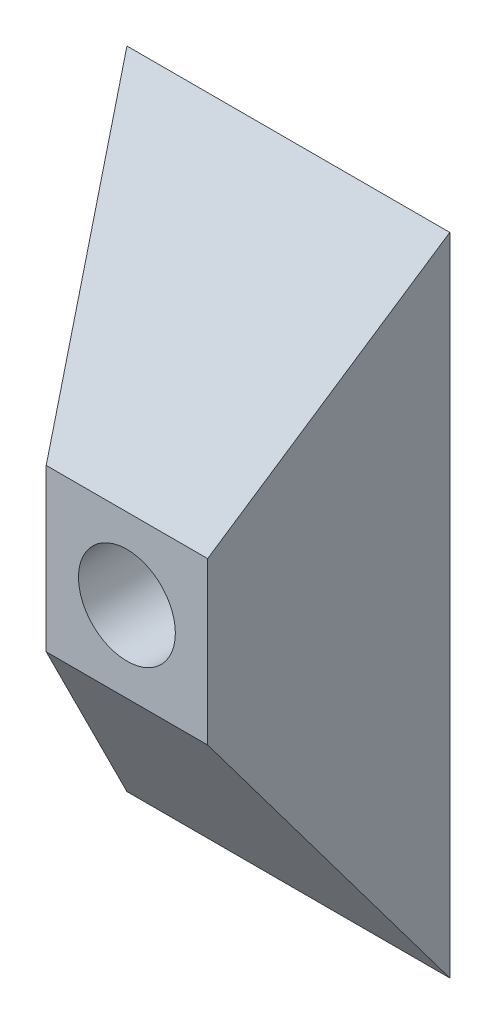
SolidWorks part; units mm, degrees
ref_plane "Alzado" through (0, 0, 0) normal (0, 0, 1) x (1, 0, 0)
ref_plane "Planta" through (0, 0, 0) normal (0, 1, 0) x (1, 0, 0)
ref_plane "Vista lateral" through (0, 0, 0) normal (1, 0, 0) x (0, 0, -1)
sketch "Croquis1" plane through (0, 0, 0) normal (0, 0, 1) x (1, 0, 0)
  line L1 (-5, -10) -> (5, -10)
  line L2 (-5, -10) -> (-5, 10)
  line L3 (-5, 10) -> (5, 10)
  line L4 (5, -10) -> (5, 10)
  line L5 (-5, -10) -> (5, 10) construction
  line L6 (-5, 10) -> (5, -10) construction
  point P0 (0, 0)
  dimension "D1" = 10
  dimension "D2" = 20
ref_plane "Plano1" through (0, 0, 5) normal (0, 0, 1) x (1, 0, 0)
sketch "Croquis9" plane through (0, 0, 5) normal (0, 0, 1) x (1, 0, 0)
  line L1 (-2.5, 2.5) -> (2.5, 2.5)
  line L2 (-2.5, 2.5) -> (-2.5, -2.5)
  line L3 (-2.5, -2.5) -> (2.5, -2.5)
  line L4 (2.5, 2.5) -> (2.5, -2.5)
  line L5 (-2.5, 2.5) -> (2.5, -2.5) construction
  line L6 (-2.5, -2.5) -> (2.5, 2.5) construction
  point P0 (0, 0)
  dimension "D1" = 5
loft "Recubrir1" add profiles "Croquis1", "Croquis9" connector at (5, -10, 0) connector at (2.5, -2.5, 5)
sketch "Croquis10" plane through (0, 0, 5) normal (0, 0, 1) x (1, 0, 0)
  circle A0 centre (0, 0) radius 1.5
  dimension "D1" = 3
extrude "Cortar-Extruir1" cut sketch "Croquis10" against normal blind 5
sketch "Croquis11" plane through (0, 0, 0) normal (0, 0, -1) x (-1, 0, 0)
  circle A0 centre (0, 0) radius 2.5
  dimension "D1" = 5
extrude "Cortar-Extruir2" cut sketch "Croquis11" against normal blind 2
